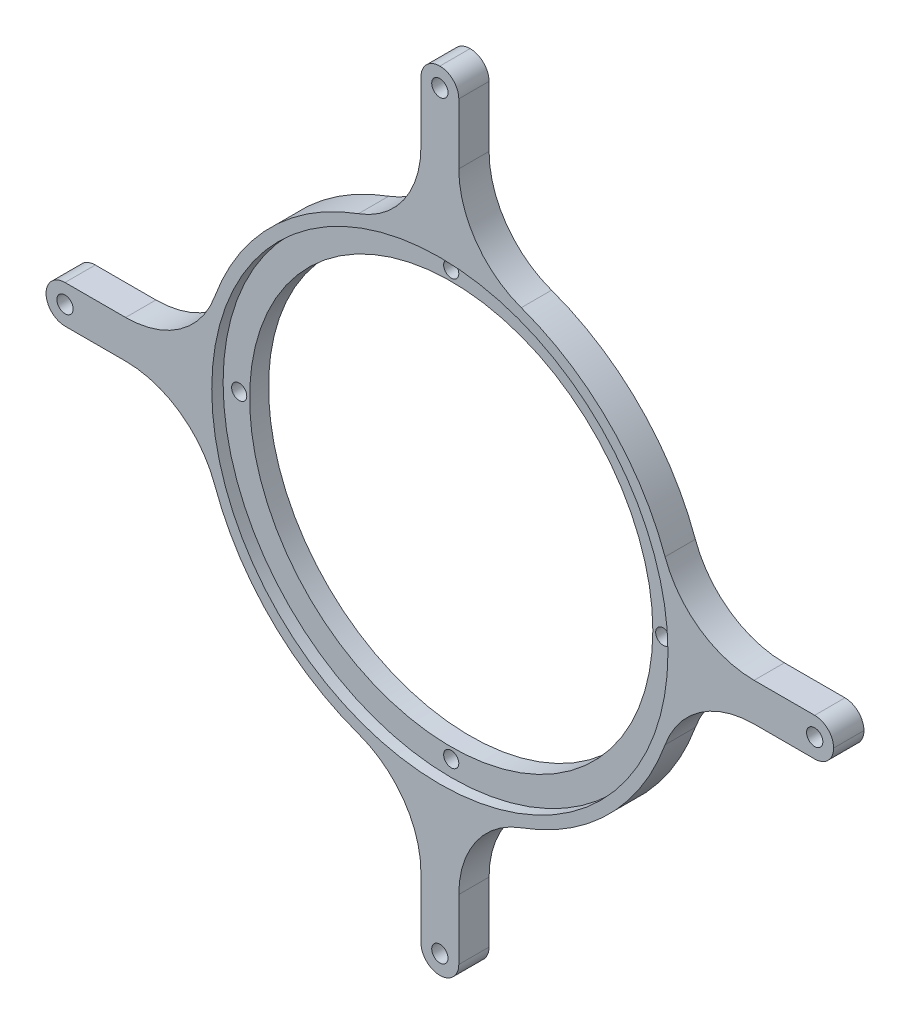
SolidWorks part; units mm, degrees
ref_plane "Alzado" through (0, 0, 0) normal (0, 0, 1) x (1, 0, 0)
ref_plane "Planta" through (0, 0, 0) normal (0, 1, 0) x (1, 0, 0)
ref_plane "Vista lateral" through (0, 0, 0) normal (1, 0, 0) x (0, 0, -1)
sketch "Croquis1" plane through (0, 0, 0) normal (0, 0, 1) x (1, 0, 0)
  circle A0 centre (0, 0) radius 60.25
  circle A2 centre (0, 56) radius 2
  circle A3 centre (0, 0) radius 53.25
  circle A4 centre (56, 0) radius 2
  circle A5 centre (0, -56) radius 2
  circle A6 centre (-56, 0) radius 2
  point P6 (0, 0)
  point P9 (0, 0)
  point P15 (0, 0)
  dimension "D1" = 120.5
  dimension "D2" = 56
  dimension "D3" = 4
  dimension "D4" = 7
  dimension "D5" = 4
extrude "Saliente-Extruir1" add sketch "Croquis1" along normal blind 5
extrude "Extruir-Lámina1" add sketch "Croquis1<2>" along normal blind 8 thin contours A0 thin type one direction wall 3
sketch "Croquis1<2>" plane through (0, 0, 0) normal (0, 0, 1) x (1, 0, 0) same geometry as "Croquis1"
sketch "Croquis2" plane through (0, 0, 0) normal (0, 0, 1) x (1, 0, 0)
  line L1 (-5, 63.0521) -> (5, 63.0521)
  line L2 (-5, 63.0521) -> (-5, 104)
  line L3 (-5, 104) -> (5, 104)
  line L4 (5, 63.0521) -> (5, 104)
  line L5 (63.0521, 5) -> (104, 5)
  line L6 (63.0521, 5) -> (63.0521, -5)
  line L7 (63.0521, -5) -> (104, -5)
  line L8 (104, 5) -> (104, -5)
  line L9 (5, -63.0521) -> (5, -104)
  line L10 (5, -63.0521) -> (-5, -63.0521)
  line L11 (-5, -63.0521) -> (-5, -104)
  line L12 (5, -104) -> (-5, -104)
  line L13 (-63.0521, -5) -> (-104, -5)
  line L14 (-63.0521, -5) -> (-63.0521, 5)
  line L15 (-63.0521, 5) -> (-104, 5)
  line L16 (-104, -5) -> (-104, 5)
  circle A0 centre (0, 0) radius 63.25 construction
  circle A1 centre (0, 99) radius 1.25
  circle A2 centre (99, 0) radius 1.25
  circle A3 centre (0, -99) radius 1.25
  circle A4 centre (-99, 0) radius 1.25
  point P6 (0, 104)
  point P10 (0, 0)
  point P13 (0, 0)
  point P31 (0, 0)
  point P33 (63.0521, 0)
  point P34 (0, 0)
  dimension "D2" = 2.5
  dimension "D1" = 10
  dimension "D3" = 5
  dimension "D4" = 4
  dimension "D5" = 198
extrude "Saliente-Extruir2" add sketch "Croquis2" along normal blind 8
fillet "Redondeo1" radius 25 8 edges at (-5, 63.0521, 4) (-63.0521, 5, 4) (-63.0521, -5, 4) (-5, -63.0521, 4) (5, -63.0521, 4) (63.0521, -5, 4) (63.0521, 5, 4) (5, 63.0521, 4)
sketch "Croquis3" plane through (0, 0, 8) normal (0, 0, 1) x (1, 0, 0)
  circle A0 centre (0, 99) radius 2.15
  circle A1 centre (99, 0) radius 2.15
  circle A2 centre (0, -99) radius 2.15
  circle A3 centre (-99, 0) radius 2.15
  point P3 (0, 0)
  point P4 (0, 0)
  point P5 (0, 1.3073)
  point P12 (0, 0)
  point P13 (0, 7.2914)
  point P15 (0, 0)
  dimension "D1" = 4.3
  dimension "D2" = 4
extrude "Cortar-Extruir1" cut sketch "Croquis3" against normal blind 5
fillet "Redondeo2" radius 5 8 edges at (-104, -5, 4) (-104, 5, 4) (-5, -104, 4) (5, -104, 4) (104, -5, 4) (104, 5, 4) (5, 104, 4) (-5, 104, 4)
